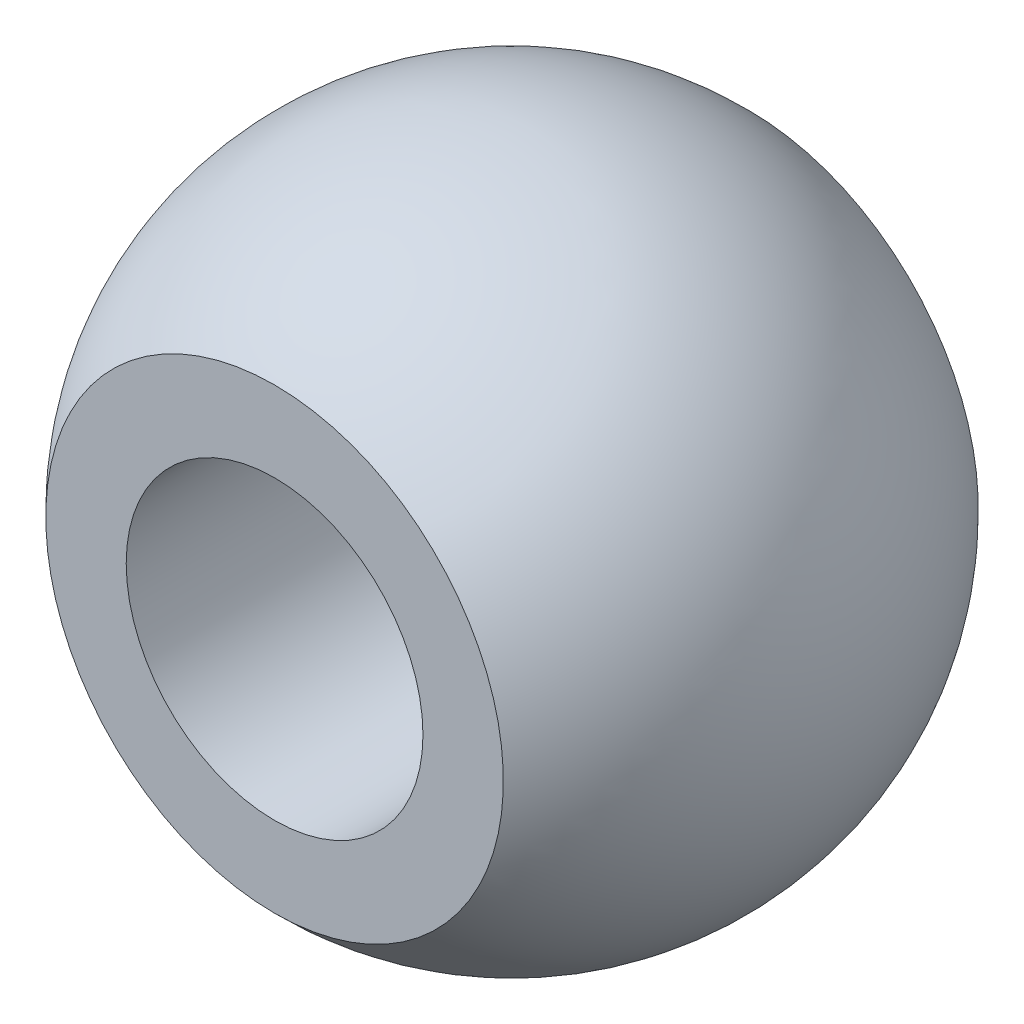
SolidWorks part; units mm, degrees
material "PW100:Mi:0:3:C1:0:1:2:Re:26:"
ref_plane "Front" through (0, 0, 0) normal (0, 0, 1) x (1, 0, 0)
ref_plane "Top" through (0, 0, 0) normal (0, 1, 0) x (1, 0, 0)
ref_plane "Right" through (0, 0, 0) normal (1, 0, 0) x (0, 0, -1)
sketch "Support-Right-Head" plane through (0, 0, 0) normal (1, 0, 0) x (0, 0, -1)
  line L0 (-4, 0) -> (4, 0) construction
  line L18 (0, -5.555) -> (0, 5.555) construction
  line L19 (-4, 2.5) -> (4, 2.5)
  line L20 (-4, 3.8546) -> (4, 3.8546)
  line L21 (-4, 3.8546) -> (-4, -3.8546)
  line L22 (-4, -3.8546) -> (4, -3.8546)
  line L23 (4, 3.8546) -> (4, -3.8546)
  line L24 (-4, -2.5) -> (4, -2.5)
  circle A1 centre (0, 0) radius 5.555
  point P5 (0, 0)
  dimension "Diam-Inner-Joint" = 5
  dimension "Depth-Joint" = 8
  dimension "Diam" = 11.11
  dimension "Diam-Outer-Joint" = 7.7092
ref_axis "Ref-Axis-Center" through (0, 51.5675, 0) along (0, -1, 0)
sketch "Sketch26" plane through (0, 0, 0) normal (1, 0, 0) x (0, 0, -1)
  line L0 (-4, 0) -> (4, 0) construction
  line L1 (4, 3.8546) -> (4, -3.8546) construction
  line L2 (-4, 2.5) -> (4, 2.5) construction
  line L3 (-4, 3.8546) -> (-4, -3.8546) construction
  line L4 (-4, 0) -> (4, 0) construction
  line L5 (4, 3.8546) -> (4, 2.5)
  line L6 (-4, 2.5) -> (4, 2.5)
  line L7 (-4, 3.8546) -> (-4, 2.5)
  circle A0 centre (0, 0) radius 5.555 construction
  arc A1 (4, 3.8546) -> (-4, 3.8546) centre (0, 0) ccw
revolve "Body-Joint" add sketch "Sketch26" angle 360 about L4
fillet "fillet" [suppressed] radius 0.3
other "冻结***"
